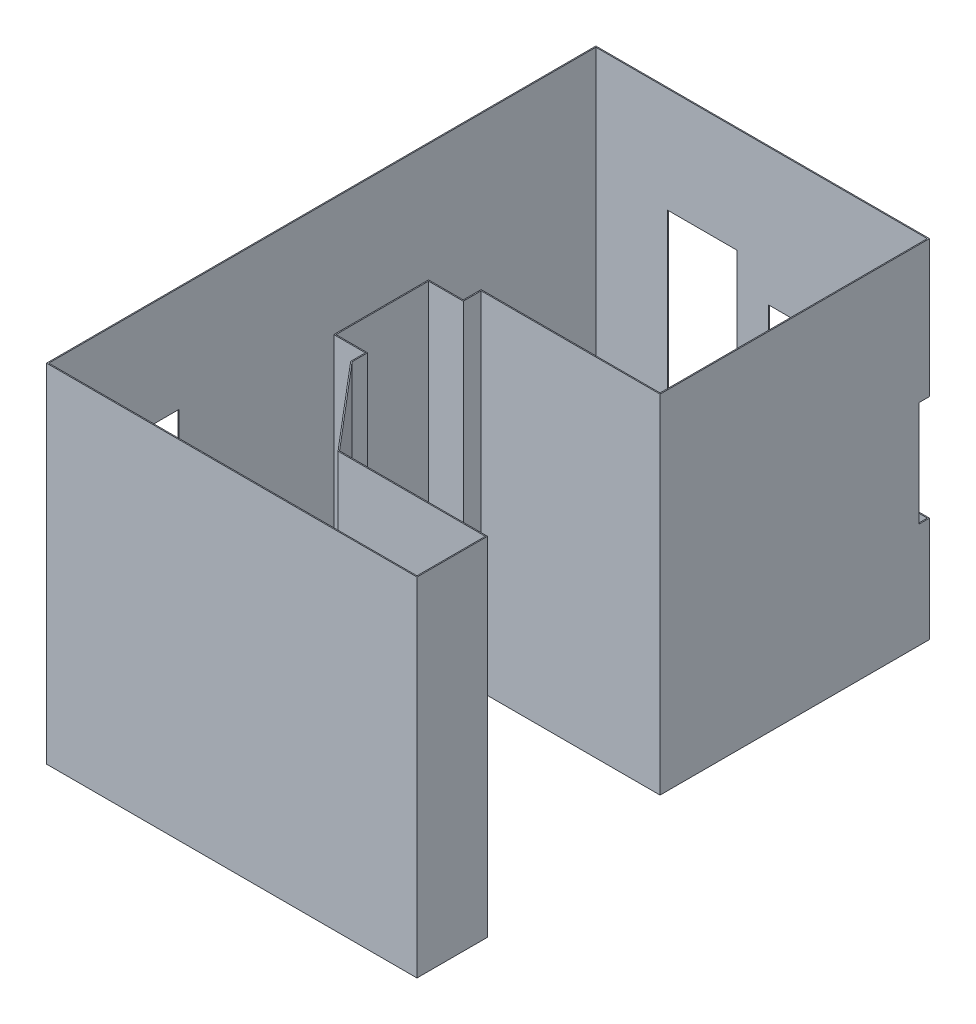
SolidWorks part; units mm, degrees
ref_plane "Спереди" through (0, 0, 0) normal (0, 0, 1) x (1, 0, 0)
ref_plane "Сверху" through (0, 0, 0) normal (0, 1, 0) x (1, 0, 0)
ref_plane "Справа" through (0, 0, 0) normal (1, 0, 0) x (0, 0, -1)
sketch "Эскиз1" plane through (0, 0, 0) normal (0, 1, 0) x (1, 0, 0)
  line L0 (0, 0) -> (0, 65)
  line L1 (0, 0) -> (-350, 0)
  line L2 (0, 65) -> (-140, 65)
  line L3 (-35.0074, 520) -> (-350, 520)
  line L4 (-350, 0) -> (-350, 520)
  line L5 (-140, 65) -> (-208.0074, 145)
  line L6 (-208.0074, 145) -> (-208.0074, 159)
  line L7 (-208.0074, 159) -> (-238.0074, 159)
  line L8 (-238.0074, 159) -> (-238.0074, 249)
  line L9 (-238.0074, 249) -> (-205.0074, 249)
  line L10 (-205.0074, 249) -> (-205.0074, 266)
  line L11 (-205.0074, 266) -> (-35.0074, 266)
  line L12 (-35.0074, 266) -> (-35.0074, 520)
  dimension "D2" = 350
  dimension "D3" = 65
  dimension "D4" = 140
  dimension "D5" = 105
  dimension "D6" = 14
  dimension "D7" = 30
  dimension "D8" = 90
  dimension "D9" = 170
  dimension "D10" = 33
  dimension "D11" = 17
  dimension "D12" = 520
  dimension "D13" = 254
  dimension "D14" = 90
extrude "Вытянуть-Тонкостенный2" add sketch "Эскиз1" along normal blind 330 thin thin type one direction wall 1
sketch "Эскиз2" plane through (0, 0, -521) normal (0, 0, -1) x (-1, 0, 0)
  line L0 (351, 330) -> (351, 0) construction
  line L1 (282, 10) -> (216, 10)
  line L2 (282, 10) -> (282, 230)
  line L3 (282, 230) -> (216, 230)
  line L4 (216, 10) -> (216, 230)
  line L5 (34.0074, 0) -> (351, 0) construction
  line L7 (186, 200) -> (32, 200)
  line L8 (186, 200) -> (186, 100)
  line L9 (186, 100) -> (32, 100)
  line L10 (32, 200) -> (32, 100)
  dimension "D1" = 69
  dimension "D2" = 66
  dimension "D3" = 10
  dimension "D4" = 220
  dimension "D5" = 154
  dimension "D6" = 100
  dimension "D7" = 30
  dimension "D8" = 100
extrude "Вырез-Вытянуть1" cut sketch "Эскиз2" against normal blind 10
sketch "Эскиз5" plane through (-351, 0, 0) normal (-1, 0, 0) x (0, 0, 1)
  line L0 (1, 330) -> (1, 0) construction
  line L1 (-124, 230) -> (-42, 230)
  line L2 (-124, 230) -> (-124, 10)
  line L3 (-124, 10) -> (-42, 10)
  line L4 (-42, 230) -> (-42, 10)
  line L5 (-521, 0) -> (1, 0) construction
  dimension "D1" = 220
  dimension "D2" = 82
  dimension "D3" = 43
  dimension "D4" = 10
extrude "Вырез-Вытянуть3" cut sketch "Эскиз5" against normal blind 10
